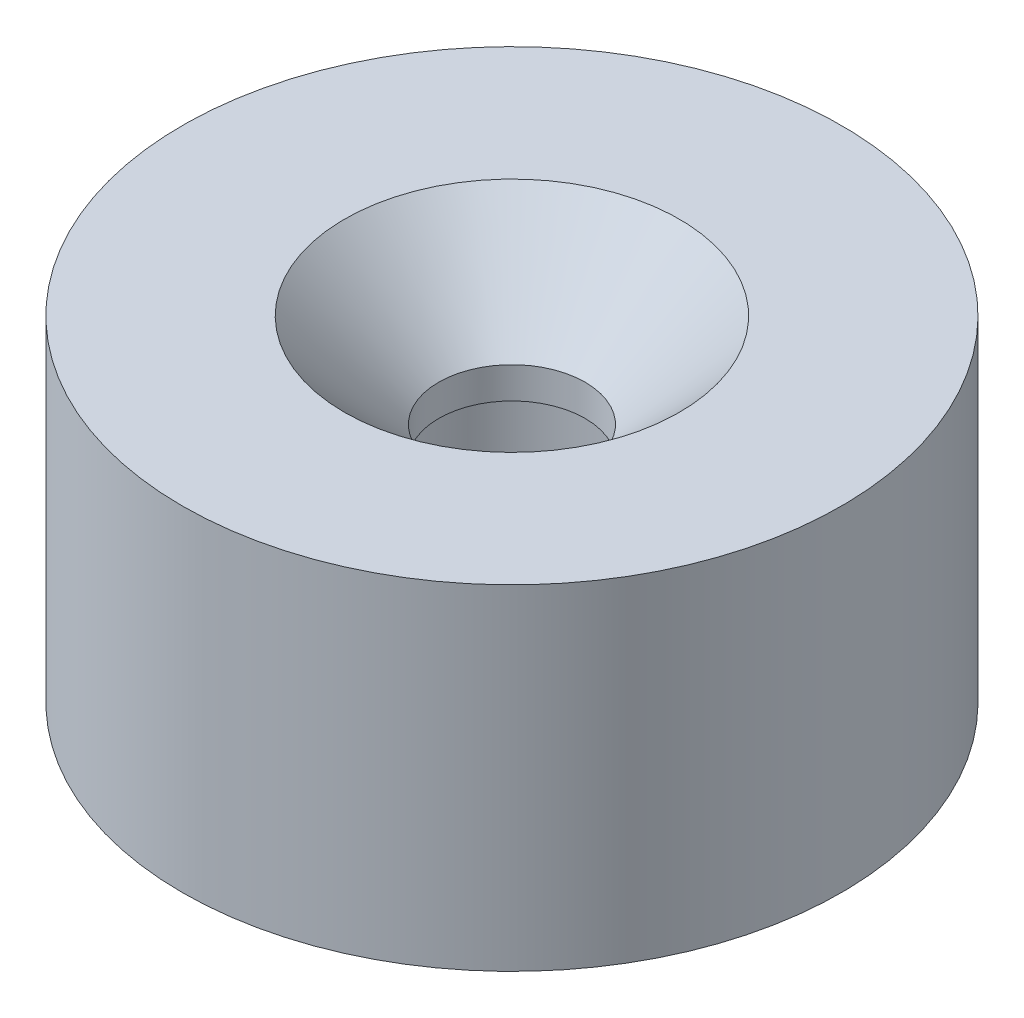
SolidWorks part; units mm, degrees
ref_plane "Front Plane" through (0, 0, 0) normal (0, 0, 1) x (1, 0, 0)
ref_plane "Top Plane" through (0, 0, 0) normal (0, 1, 0) x (1, 0, 0)
ref_plane "Right Plane" through (0, 0, 0) normal (1, 0, 0) x (0, 0, -1)
sketch "Sketch1" plane through (0, 0, 0) normal (0, 1, 0) x (1, 0, 0)
  circle A0 centre (0, 0) radius 7.875
  circle A1 centre (0, 0) radius 1.75
  dimension "D1" = 15.75
  dimension "D2" = 3.5
extrude "Boss-Extrude1" add sketch "Sketch1" along normal blind 8
sketch "Sketch2" plane through (0, 8, 0) normal (0, 1, 0) x (1, 0, 0)
  circle A0 centre (0, 0) radius 4
  circle A1 centre (0, 0) radius 1.75 construction
  dimension "D1" = 8
extrude "Cut-Extrude1" cut sketch "Sketch2" against normal blind 3 draft 45
sketch "Sketch3" plane through (0, 0, 0) normal (0, -1, 0) x (-1, 0, 0)
  circle A0 centre (0, 0) radius 4
  circle A1 centre (0, 0) radius 1.75 construction
  dimension "D1" = 8
extrude "Cut-Extrude2" cut sketch "Sketch3" against normal blind 5
sketch "Sketch4" plane through (0, 5, 0) normal (0, -1, 0) x (1, 0, 0)
  circle A0 centre (0, 0) radius 2.5
  circle A1 centre (0, 0) radius 4
  circle A2 centre (0, 0) radius 4 construction
  dimension "D1" = 5
extrude "Boss-Extrude2" add sketch "Sketch4" along normal blind 2
sketch "Sketch5" [suppressed] plane through (0, 8, 0) normal (0, 1, 0) x (1, 0, 0)
  line L0 (4.437, 6.506) -> (4.437, -6.506)
  line L1 (3.937, -6.9653) -> (3.937, 4.6059) construction
  circle A0 centre (0, 0) radius 7.875 construction
  arc A1 (4.437, -6.506) -> (4.437, 6.506) centre (0, 0) ccw
  point P6 (0, 0)
  point P8 (0, 0)
  point P9 (0, 0)
  point P10 (4.5567, 2.2048)
  point P13 (0, 0)
  point P14 (0, 0)
  dimension "D1" = 0.5
extrude "Boss-Extrude3" [suppressed] add sketch "Sketch5" along normal blind 8
sketch "Sketch6" [suppressed] plane through (3.937, 0, 0) normal (1, 0, 0) x (0, 0, -1)
  line L0 (14.052, 7.7042) -> (-6.463, 7.7042) construction
  line L1 (-6.506, 16) -> (-3.506, 16)
  line L2 (-6.506, 16) -> (-6.506, 7.7042)
  line L3 (-6.506, 7.7042) -> (-3.506, 7.7042)
  line L4 (-3.506, 16) -> (-3.506, 7.7042)
  line L5 (0, 16) -> (0, 7.7042) construction
  line L6 (6.506, 16) -> (-6.506, 16) construction
  line L7 (3.506, 16) -> (3.506, 7.7042)
  line L8 (6.506, 7.7042) -> (3.506, 7.7042)
  line L9 (6.506, 16) -> (6.506, 7.7042)
  line L10 (6.506, 16) -> (3.506, 16)
  dimension "D1" = 3
extrude "Cut-Extrude3" [suppressed] cut sketch "Sketch6" along normal through all
sketch "Sketch7" plane through (0, 8, 0) normal (0, 1, 0) x (1, 0, 0)
  circle A0 centre (0, 0) radius 1.25
  circle A1 centre (0, 0) radius 2.5
  dimension "D1" = 2.5
  dimension "D2" = 5
extrude "Boss-Extrude4" [suppressed] add sketch "Sketch7" along normal blind 10 separate body
sketch "Sketch9" plane through (11.2113, 0, 0) normal (1, 0, 0) x (0, 0, -1)
  circle A0 centre (-6.463, 18.7042) radius 6.35
  circle A1 centre (-6.463, 18.7042) radius 6.35 construction
extrude "Cut-Extrude4" [suppressed] cut sketch "Sketch9" against normal through all
sketch "Sketch10" plane through (6.1024, 0, 0) normal (1, 0, 0) x (0, 0, -1)
  circle A0 centre (8.6773, 18.7042) radius 8.5
  dimension "D1" = 17
extrude "Cut-Extrude5" [suppressed] cut sketch "Sketch10" against normal through all
ref_plane "Plane1" [suppressed] through (2.5, 0, 0) normal (1, 0, 0) x (0, 0, -1)
